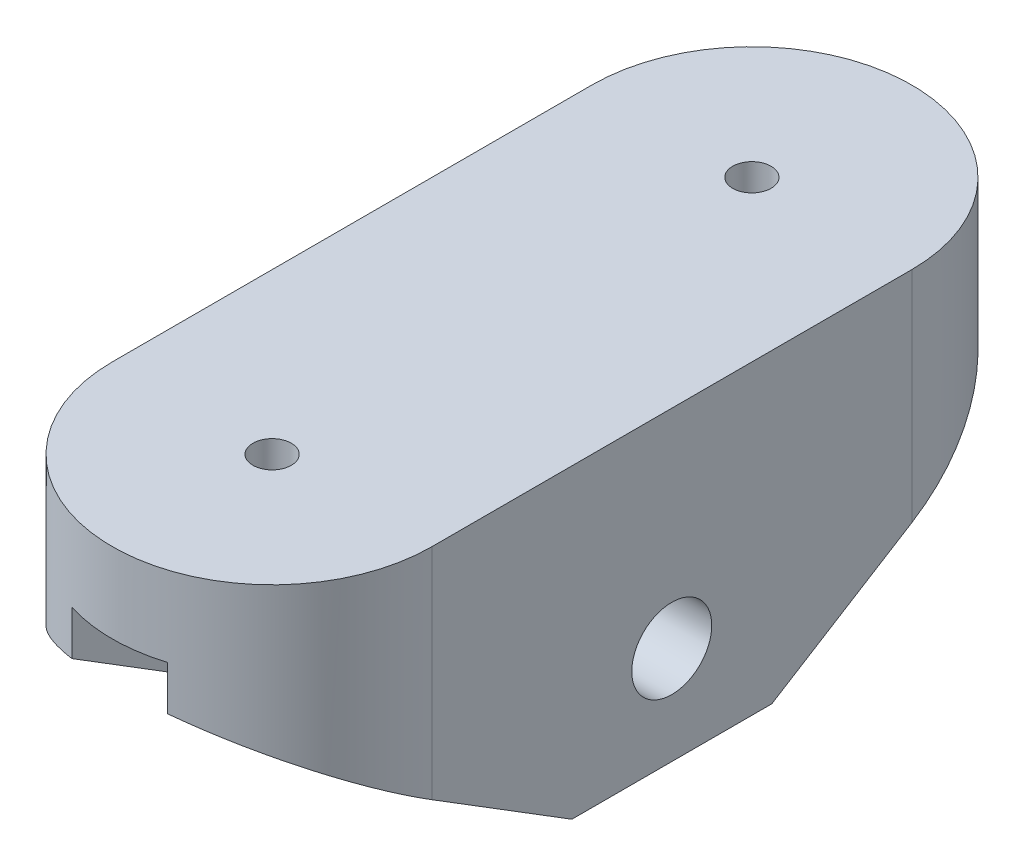
SolidWorks part; units mm, degrees
ref_plane "Front Plane" through (0, 0, 0) normal (0, 0, 1) x (1, 0, 0)
ref_plane "Top Plane" through (0, 0, 0) normal (0, 1, 0) x (1, 0, 0)
ref_plane "Right Plane" through (0, 0, 0) normal (1, 0, 0) x (0, 0, -1)
sketch "Sketch1" plane through (0, 0, 0) normal (0, 1, 0) x (1, 0, 0)
  line L0 (0, 0) -> (0, -38.1) construction
  line L1 (12.7, 0) -> (12.7, -38.1)
  line L2 (-12.7, 0) -> (-12.7, -38.1)
  line L3 (0, -35.5951) -> (-2.1693, -36.8476) construction
  line L4 (-2.1693, -36.8476) -> (-2.1693, -39.3524) construction
  line L5 (-2.1693, -39.3524) -> (0, -40.6049) construction
  line L6 (0, -40.6049) -> (2.1693, -39.3524) construction
  line L7 (2.1693, -39.3524) -> (2.1693, -36.8476) construction
  line L8 (2.1693, -36.8476) -> (0, -35.5951) construction
  line L9 (0, 3.0794) -> (-2.1693, 1.8269) construction
  line L10 (-2.1693, 1.8269) -> (-2.1693, -0.678) construction
  line L11 (-2.1693, -0.678) -> (0, -1.9304) construction
  line L12 (0, -1.9304) -> (2.1693, -0.678) construction
  line L13 (2.1693, -0.678) -> (2.1693, 1.8269) construction
  line L14 (2.1693, 1.8269) -> (0, 3.0794) construction
  arc A0 (12.7, 0) -> (-12.7, 0) centre (0, 0) ccw
  arc A1 (-12.7, -38.1) -> (12.7, -38.1) centre (0, -38.1) ccw
  circle A2 centre (0, -38.1) radius 2.1693 construction
  circle A3 centre (0, 0.5745) radius 2.1693 construction
  circle A4 centre (0, -38.1) radius 1.524 construction
  circle A5 centre (0, 0.5745) radius 1.524 construction
  point P3 (0, -19.05)
extrude "Boss-Extrude1" add sketch "Sketch1" against normal blind 6.35
sketch "Sketch2" plane through (0, 0, 0) normal (1, 0, 0) x (0, 0, -1)
  line L0 (-19.05, -6.35) -> (-19.05, -31.75) construction
  line L1 (12.7, -6.35) -> (-50.8, -6.35) construction
  line L2 (12.7, -6.35) -> (12.7, -12.7) construction
  line L3 (12.7, -12.7) -> (-11.1189, -37.0247) construction
  line L4 (-11.1189, -37.0247) -> (-26.9938, -37.0056) construction
  line L5 (-26.9938, -37.0056) -> (-50.8, -12.7) construction
  line L6 (-50.8, -12.7) -> (-50.8, -6.35) construction
  line L7 (-50.8, -6.35) -> (12.7, -6.35)
  line L8 (12.7, -6.35) -> (12.7, -9.525)
  line L9 (-19.05, -6.35) -> (-19.05, -9.525) construction
  line L10 (-11.1188, -24.3056) -> (-26.9938, -24.3056)
  line L11 (12.7, -9.525) -> (-11.1188, -24.3056)
  line L12 (-50.8, -6.35) -> (-50.8, -9.525)
  line L13 (-50.8, -9.525) -> (-26.9938, -24.3056)
  circle A0 centre (-19.05, -31.75) radius 9.525 construction
  circle A1 centre (-19.05, -19.05) radius 9.525 construction
extrude "Boss-Extrude3" add sketch "Sketch2" along normal through all and the other way through all
sketch "Sketch10" plane through (0, -6.35, 0) normal (0, 1, 0) x (1, 0, 0)
  line L0 (0, 0) -> (0, -38.1) construction
  line L1 (12.7, 0) -> (12.7, -38.1)
  line L2 (-12.7, 0) -> (-12.7, -38.1)
  line L3 (-12.7, 0) -> (12.7, -38.1) construction
  line L4 (12.7, -38.1) -> (0, -19.05) construction
  line L6 (-12.7, -50.8) -> (12.7, -50.8)
  line L7 (-12.7, -50.8) -> (-12.7, 12.7)
  line L8 (-12.7, 12.7) -> (12.7, 12.7)
  line L9 (12.7, -50.8) -> (12.7, 12.7)
  line L10 (-12.7, -50.8) -> (12.7, 12.7) construction
  line L11 (-12.7, 12.7) -> (12.7, -50.8) construction
  arc A0 (12.7, 0) -> (-12.7, 0) centre (0, 0) ccw
  arc A1 (-12.7, -38.1) -> (12.7, -38.1) centre (0, -38.1) ccw
  arc A2 (-12.7, -38.1) -> (12.7, -38.1) centre (0, -38.1) ccw construction
  arc A3 (0, -50.8) -> (12.7, -38.1) centre (0, -38.1) ccw construction
  point P2 (0, -19.05)
  arc M1 (0, 12.7) -> (12.7, 0) centre (0, 0) cw
  line M2 (12.7, 0) -> (12.7, 12.7)
  line M17 (12.7, 12.7) -> (0, 12.7)
sketch "Sketch11" plane through (0, 0, 0) normal (0, 0, 1) x (1, 0, 0)
  line L0 (0, 0) -> (0, -6.35) construction
  line L2 (12.7, -6.35) -> (0, -6.35) construction
  line L3 (-3.7847, -35.5514) -> (3.81, -35.5514)
  line L4 (-3.7847, -35.5514) -> (-3.7847, -6.35)
  line L5 (-3.7847, -6.35) -> (3.81, -6.35)
  line L6 (3.81, -35.5514) -> (3.81, -6.35)
  line L7 (-3.7847, -35.5514) -> (3.81, -6.35) construction
  line L8 (-3.7847, -6.35) -> (3.81, -35.5514) construction
  point P2 (0.0126, -20.9507)
extrude "Cut-Extrude13" cut sketch "Sketch11" against normal through all and the other way through all
extrude "Cut-Extrude19" cut sketch "Sketch10" against normal through all contours A0 L8 L7 | M17 M1 M2 | A1 L7 L6 | A1 L6 L9 region at (9.8632, -6.35, -9.8632) region at (9.8632, -6.35, 47.9632) region at (-9.8632, -6.35, -9.8632) region at (-9.8632, -6.35, 47.9632)
sketch "Sketch16" plane through (0, -6.35, 0) normal (0, -1, 0) x (1, 0, 0)
  line L0 (0, 2.5049) -> (-2.1693, 1.2524)
  line L1 (-2.1693, 1.2524) -> (-2.1693, -1.2524)
  line L2 (-2.1693, -1.2524) -> (0, -2.5049)
  line L3 (0, -2.5049) -> (2.1693, -1.2524)
  line L4 (2.1693, -1.2524) -> (2.1693, 1.2524)
  line L5 (2.1693, 1.2524) -> (0, 2.5049)
  line L6 (0, 40.4932) -> (-2.1693, 39.2407)
  line L7 (-2.1693, 39.2407) -> (-2.1693, 36.7358)
  line L8 (-2.1693, 36.7358) -> (0, 35.4834)
  line L9 (0, 35.4834) -> (2.1693, 36.7358)
  line L10 (2.1693, 36.7358) -> (2.1693, 39.2407)
  line L11 (2.1693, 39.2407) -> (0, 40.4932)
  line L12 (-12.7, 19.05) -> (12.7, 19.05) construction
  line L13 (-12.7, 0) -> (-12.7, 38.1) construction
  line L14 (12.7, 38.1) -> (12.7, 0) construction
  line L16 (0, 0) -> (0, 38.1) construction
  circle A0 centre (0, 0) radius 2.1693 construction
  circle A1 centre (0, 37.9883) radius 2.1693 construction
  circle A2 centre (0, 0) radius 1.524 construction
  circle A3 centre (0, 37.9883) radius 1.524 construction
extrude "Cut-Extrude20" cut sketch "Sketch16" against normal blind 1.778
sketch "Sketch17" plane through (0, -4.572, 0) normal (0, -1, 0) x (1, 0, 0)
  line L1 (-12.7, 19.05) -> (12.7, 19.05) construction
  line L2 (-12.7, 0) -> (-12.7, 38.1) construction
  line L3 (12.7, 38.1) -> (12.7, 0) construction
  line L4 (0, 0) -> (0, 38.1) construction
  circle A0 centre (0, 38.1) radius 1.524
  circle A1 centre (0, 0) radius 1.524
extrude "Cut-Extrude21" cut sketch "Sketch17" against normal through all
sketch "Sketch18" plane through (-12.7, 0, 0) normal (-1, 0, 0) x (0, 0, 1)
  line L0 (19.0627, -16.5241) -> (19.0627, -19.6991) construction
  line L1 (50.8127, -6.35) -> (-12.6873, -6.35) construction
  line L2 (50.8127, -6.35) -> (50.8127, -12.7) construction
  line L6 (-12.6873, -12.7) -> (-12.6873, -6.35) construction
  line L7 (-12.6873, -6.35) -> (50.8127, -6.35) construction
  line L8 (50.8127, -6.35) -> (50.8127, -9.525) construction
  line L9 (19.0627, -6.35) -> (19.0627, -9.525) construction
  line L10 (26.9938, -24.3056) -> (11.1188, -24.3056) construction
  line L11 (50.8127, -9.525) -> (26.9938, -24.3056) construction
  line L12 (-12.6873, -6.35) -> (-12.6873, -9.525) construction
  line L13 (-12.6873, -9.525) -> (11.1188, -24.3056) construction
  circle A0 centre (19.0627, -16.5241) radius 3.175
  circle A1 centre (19.0627, -16.5241) radius 9.525 construction
  point P2 (11.1188, -24.3056)
extrude "Cut-Extrude22" cut sketch "Sketch18" against normal through all
